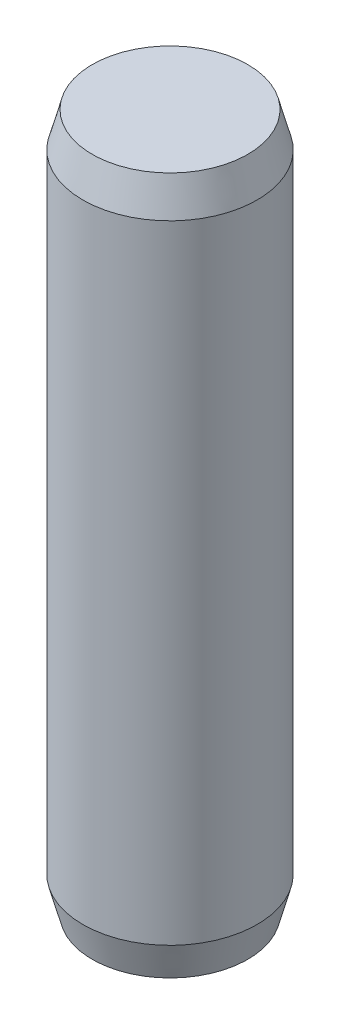
SolidWorks part; units mm, degrees
ref_plane "Спереди" through (0, 0, 0) normal (0, 0, 1) x (1, 0, 0)
ref_plane "Сверху" through (0, 0, 0) normal (0, 1, 0) x (1, 0, 0)
ref_plane "Справа" through (0, 0, 0) normal (1, 0, 0) x (0, 0, -1)
sketch "Ske" plane through (0, 0, 0) normal (0, 0, 1) x (1, 0, 0)
  line L0 (0, 0) -> (0, 11.3826) construction
  line L2 (0, 24) -> (3, 24)
  line L3 (0, 24) -> (0, 0)
  line L4 (0, 0) -> (3, 0)
  line L5 (3, 24) -> (3, 0)
  dimension "d" = 6
  dimension "l" = 24
revolve "Base-Rev" add sketch "Ske" angle 360 about L0
sketch "Ske2" plane through (0, 0, 0) normal (0, 0, 1) x (1, 0, 0)
  line L0 (0, 0) -> (0, 3.184) construction
  line L1 (3, 0) -> (3, 24) construction
  line L5 (0, 0) -> (0, -3)
  line L6 (0, -3) -> (3, -3)
  line L7 (3, 0.8) -> (3, -3)
  arc A0 (3, 0.8) -> (0, 0) centre (0.0067, 6) cw
  dimension "R" = 6
  dimension "a" = 0.8
revolve "Cut-Rev" [suppressed] cut sketch "Ske2" angle 360 about L0
chamfer "Chamfer2" distance 1.2 angle 15 1 edges at (0, 0, -3) first distance on face at (0, 24, -3)
chamfer "Chamfer1" distance 1.2 angle 15 1 edges at (0, 24, -3) first distance on face at (0, 1.2, -3)
equation "\"R@Ske2\" = \"d@Ske\""
